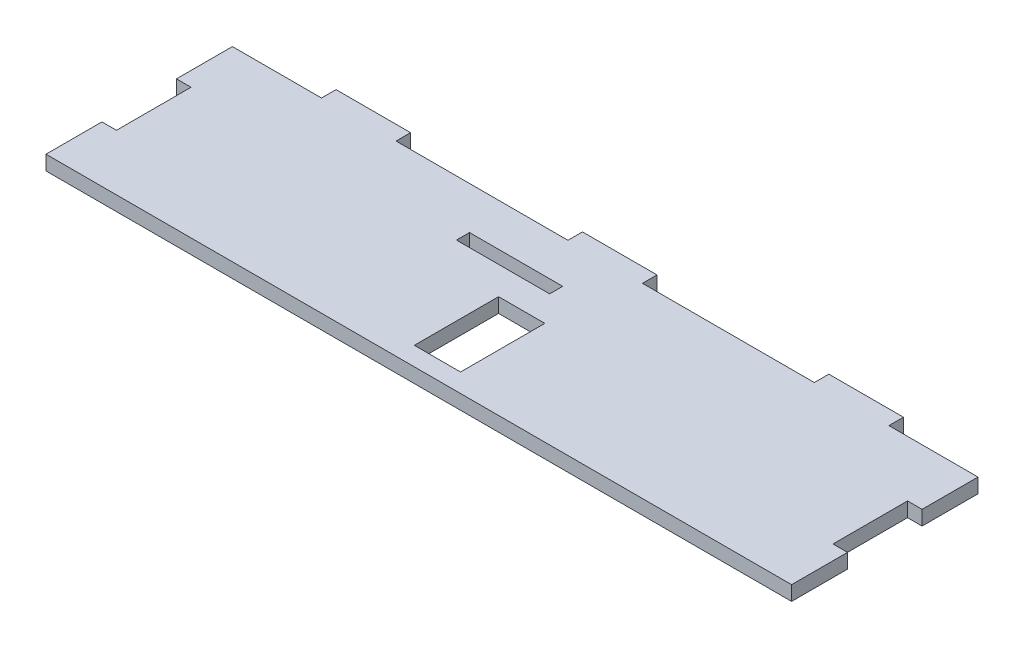
SolidWorks part; units mm, degrees
material "Very Low Density PE (SS)"
ref_plane "Front Plane" through (0, 0, 0) normal (0, 0, 1) x (1, 0, 0)
ref_plane "Top Plane" through (0, 0, 0) normal (0, 1, 0) x (1, 0, 0)
ref_plane "Right Plane" through (0, 0, 0) normal (1, 0, 0) x (0, 0, -1)
sketch "Sketch1" plane through (0, 0, 0) normal (0, 1, 0) x (1, 0, 0)
  line L0 (0, -25) -> (0, 26.95) construction
  line L1 (-100, 25) -> (-76.1, 25)
  line L2 (-100, 25) -> (-100, 10)
  line L3 (-100, -25) -> (100, -25)
  line L4 (100, 25) -> (100, 10)
  line L5 (-100, 25) -> (100, -25) construction
  line L6 (-100, -25) -> (100, 25) construction
  line L7 (76.1, 28.9) -> (56.1, 28.9)
  line L9 (-76.1, 25) -> (-76.1, 28.9)
  line L10 (-76.1, 28.9) -> (-56.1, 28.9)
  line L11 (-56.1, 25) -> (-56.1, 28.9)
  line L12 (56.1, 25) -> (56.1, 28.9)
  line L14 (76.1, 25) -> (76.1, 28.9)
  line L15 (-56.1, 25) -> (-10, 25)
  line L16 (76.1, 25) -> (100, 25)
  line L17 (10, 25) -> (56.1, 25)
  line L18 (-10, 28.9) -> (10, 28.9)
  line L19 (-10, 28.9) -> (-10, 25)
  line L21 (10, 28.9) -> (10, 25)
  line L22 (-10, 28.9) -> (10, 25) construction
  line L23 (-10, 25) -> (10, 28.9) construction
  line L24 (-100, 0) -> (100, 0) construction
  line L29 (-100, -5) -> (-100, 5)
  line L31 (100, 10) -> (96.1, 10)
  line L35 (-100, 5) -> (-100, -5) construction
  line L36 (-100, -5) -> (-100, 0)
  line L37 (100, 5) -> (100, -5) construction
  line L39 (100, 10) -> (100, 0) construction
  line L43 (100, -10) -> (96.1, -10)
  line L44 (100, -10) -> (100, 0) construction
  line L45 (-100, -10) -> (-100, 0) construction
  line L46 (-100, -10) -> (-96.1, -10)
  line L47 (-96.1, -10) -> (-96.1, 0)
  line L48 (-100, 0) -> (-96.1, 0)
  line L49 (-100, 0) -> (-96.1, 0)
  line L50 (-96.1, 10) -> (-96.1, 0)
  line L51 (-100, 10) -> (-96.1, 10)
  line L52 (-100, 10) -> (-100, 0) construction
  line L53 (100, 10) -> (100, 0) construction
  line L55 (100, 0) -> (100, -10) construction
  line L56 (100, -10) -> (100, -25)
  line L57 (-100, 10) -> (-100, 0) construction
  line L58 (-100, 0) -> (-100, 5)
  line L59 (-100, 0) -> (-100, -10) construction
  line L60 (-100, -10) -> (-100, -25)
  line L61 (0, 10.1) -> (-25, 10.1)
  line L62 (-6.2, 2.6) -> (6.2, 2.6)
  line L63 (-6.2, 2.6) -> (-6.2, -20)
  line L64 (-6.2, -20) -> (6.2, -20)
  line L65 (6.2, 2.6) -> (6.2, -20)
  line L66 (-6.2, 2.6) -> (6.2, -20) construction
  line L67 (-6.2, -20) -> (6.2, 2.6) construction
  line L72 (-25, 13.6) -> (-25, 10.1)
  line L73 (0, 13.6) -> (-25, 13.6)
  line L74 (0, 13.6) -> (0, 10.1)
  line L75 (96.1, 10) -> (96.1, -10)
  point P0 (0, 0)
  point P18 (0, 26.95)
  point P43 (0, -8.7)
  dimension "D8" = 20
  dimension "D10" = 22.6
  dimension "D12" = 5
  dimension "D1" = 200
  dimension "D2" = 50
  dimension "D3" = 20
  dimension "D4" = 3.9
  dimension "D5" = 23.9
  dimension "D6" = 20
  dimension "D7" = 3.9
  dimension "D9" = 11.4
  dimension "D11" = 12.4
  dimension "D13" = 25
  dimension "D14" = 3.5
extrude "Boss-Extrude1" add sketch "Sketch1" along normal blind 3.9 contours L46 L60 L3 L56 L43 L31 L4 L16 L14 L7 L12 L17 L21 L18 L19 L15 L11 L10 L9 L1 L2 L51 L50 L49 L58 L29 L36 L48 L47 L62 L65 L64 L63 L73 L74 L61 L72 | L65 L62 L63 L64 region at (-88.05, 0, -22.9286) region at (0, 0, 8.7)
extrude "Cut-Extrude3" cut sketch "Sketch1<3>" along normal through all contours L65 L62 L63 L64 region at (0, 0, 8.7)
sketch "Sketch1<3>" plane through (0, 0, 0) normal (0, 1, 0) x (1, 0, 0) same geometry as "Sketch1"
